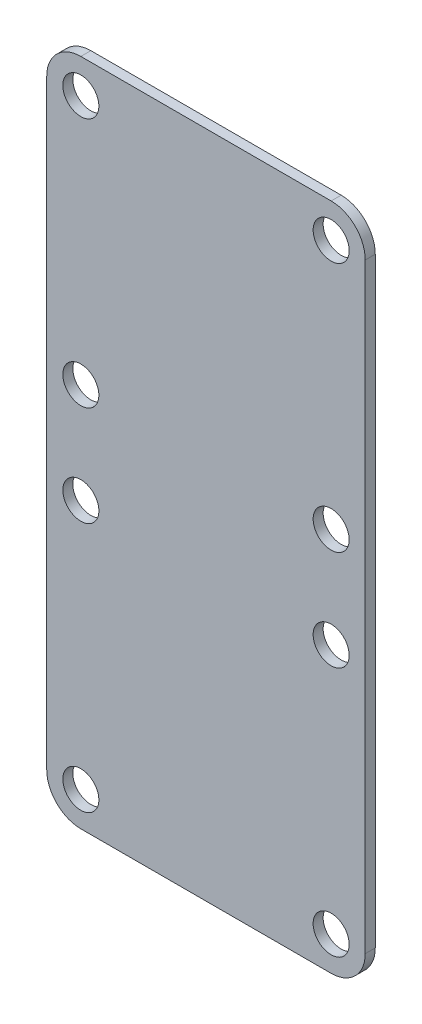
SolidWorks part; units mm, degrees
ref_plane "Front Plane" through (0, 0, 0) normal (0, 0, 1) x (1, 0, 0)
ref_plane "Top Plane" through (0, 0, 0) normal (0, 1, 0) x (1, 0, 0)
ref_plane "Right Plane" through (0, 0, 0) normal (1, 0, 0) x (0, 0, -1)
sketch "Sketch1" plane through (0, 0, 0) normal (0, 0, 1) x (1, 0, 0)
  line L18 (31.81, 60) -> (31.81, -60)
  line L20 (-31.81, 60) -> (-31.81, -60)
  line L21 (-25, -66.81) -> (25, -66.81)
  line L23 (-25, 66.81) -> (25, 66.81)
  circle A0 centre (-25, 60) radius 3.6
  circle A1 centre (25, 60) radius 3.6
  circle A2 centre (-25, 10) radius 3.6
  circle A3 centre (25, 10) radius 3.6
  circle A28 centre (-25, -10) radius 3.6
  circle A29 centre (25, -10) radius 3.6
  circle A30 centre (-25, -60) radius 3.6
  circle A31 centre (25, -60) radius 3.6
  arc A56 (31.81, 60) -> (25, 66.81) centre (25, 60) ccw
  arc A57 (-31.81, -60) -> (-25, -66.81) centre (-25, -60) ccw
  arc A58 (25, -66.81) -> (31.81, -60) centre (25, -60) ccw
  arc A59 (-25, 66.81) -> (-31.81, 60) centre (-25, 60) ccw
extrude "Boss-Extrude1" add sketch "Sketch1" along normal blind 2
